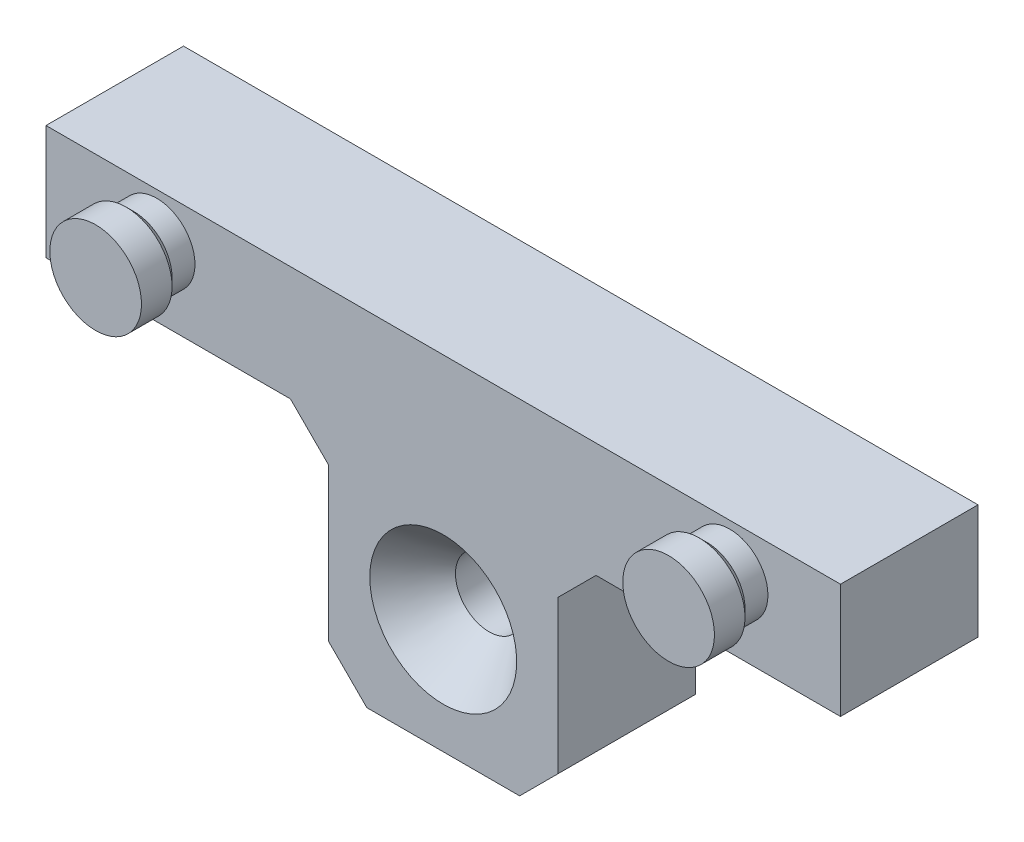
SolidWorks part; units mm, degrees
ref_plane "Front Plane" through (0, 0, 0) normal (0, 0, 1) x (1, 0, 0)
ref_plane "Top Plane" through (0, 0, 0) normal (0, 1, 0) x (1, 0, 0)
ref_plane "Right Plane" through (0, 0, 0) normal (1, 0, 0) x (0, 0, -1)
sketch "Sketch1" plane through (0, 0, 0) normal (0, 0, 1) x (1, 0, 0)
  line L0 (0, -3) -> (52, -3) construction
  line L1 (0, 0) -> (52, 0)
  line L2 (0, 0) -> (0, -7.5)
  line L3 (0, -7.5) -> (52, -7.5)
  line L4 (52, 0) -> (52, -7.5)
  line L5 (26, -3) -> (26, 0) construction
  line L6 (26, -7.5) -> (26, -22.5) construction
  line L8 (18.5, -7.5) -> (33.5, -7.5)
  line L9 (18.5, -7.5) -> (18.5, -22.5)
  line L10 (18.5, -22.5) -> (33.5, -22.5)
  line L11 (33.5, -7.5) -> (33.5, -22.5)
  line L12 (18.5, -7.5) -> (33.5, -22.5) construction
  line L13 (18.5, -22.5) -> (33.5, -7.5) construction
  circle A0 centre (7.25, -3) radius 2.5
  circle A1 centre (44.75, -3) radius 2.5
  circle A2 centre (26, -15) radius 2.2
  point P15 (26, -15)
  dimension "D3" = 5
  dimension "D9" = 4.4
  dimension "D1" = 52
  dimension "D2" = 7.5
  dimension "D4" = 7.25
  dimension "D5" = 7.25
  dimension "D6" = 3
  dimension "D7" = 15
  dimension "D8" = 15
extrude "Boss-Extrude1" add sketch "Sketch1" along normal blind 9 contours L4 L1 L2 L3 A1 A0 | L11 L3 L9 L10 region at (26, -3.834, 0) region at (26, -7.7121, 0)
sketch "Sketch2" plane through (0, 0, 9) normal (0, 0, 1) x (1, 0, 0)
  circle A0 centre (7.25, -3) radius 2.5
  circle A1 centre (44.75, -3) radius 2.5
  circle A2 centre (7.25, -3) radius 2.5 construction
  circle A3 centre (44.75, -3) radius 2.5 construction
extrude "Boss-Extrude2" add sketch "Sketch2" against normal up to surface (9 mm away) and the other way blind 1.5 up to face at (47.25, -3, 0)
ref_plane "Plane1" through (0, -15, 0) normal (0, 1, 0) x (1, 0, 0)
sketch "Sketch3" plane through (0, -15, 0) normal (0, 1, 0) x (1, 0, 0)
  line L0 (26, -9) -> (30.8079, -9)
  line L1 (18.5, -9) -> (33.5, -9) construction
  line L2 (30.8079, -9) -> (28.2, -6)
  line L3 (28.2, -6) -> (26, -6)
  line L4 (26, -6) -> (26, -9)
  dimension "D1" = 2.2
  dimension "D2" = 3
  dimension "D3" = 131
revolve "Cut-Revolve1" cut sketch "Sketch3" angle 360 about L4
sketch "Sketch4" plane through (0, 0, 10.5) normal (0, 0, 1) x (1, 0, 0)
  line L0 (0, 0) -> (52, 0) construction
  circle A0 centre (7.25, -3) radius 3
  circle A1 centre (44.75, -3) radius 3
extrude "Boss-Extrude3" add sketch "Sketch4" along normal blind 2.5
chamfer "Chamfer1" distance 0.5 angle 45 2 edges at (47.75, -3, 10.5) (10.25, -3, 10.5)
chamfer "Chamfer2" distance 2.5 angle 45 4 edges at (33.5, -7.5, 4.5) (33.5, -22.5, 4.5) (18.5, -22.5, 4.5) (18.5, -7.5, 4.5)
sketch "Sketch5" plane through (0, 0, 9) normal (0, 0, 1) x (1, 0, 0)
  circle A0 centre (7.25, -3) radius 1.25
  circle A1 centre (44.75, -3) radius 1.25
  dimension "D1" = 2.5
  dimension "D2" = 2.5
extrude "Cut-Extrude1" cut sketch "Sketch5" along normal offset from surface 2 and the other way offset from surface 2 up to face at (10.25, -3, 13) other way up to face at (26, -11.25, 0)
